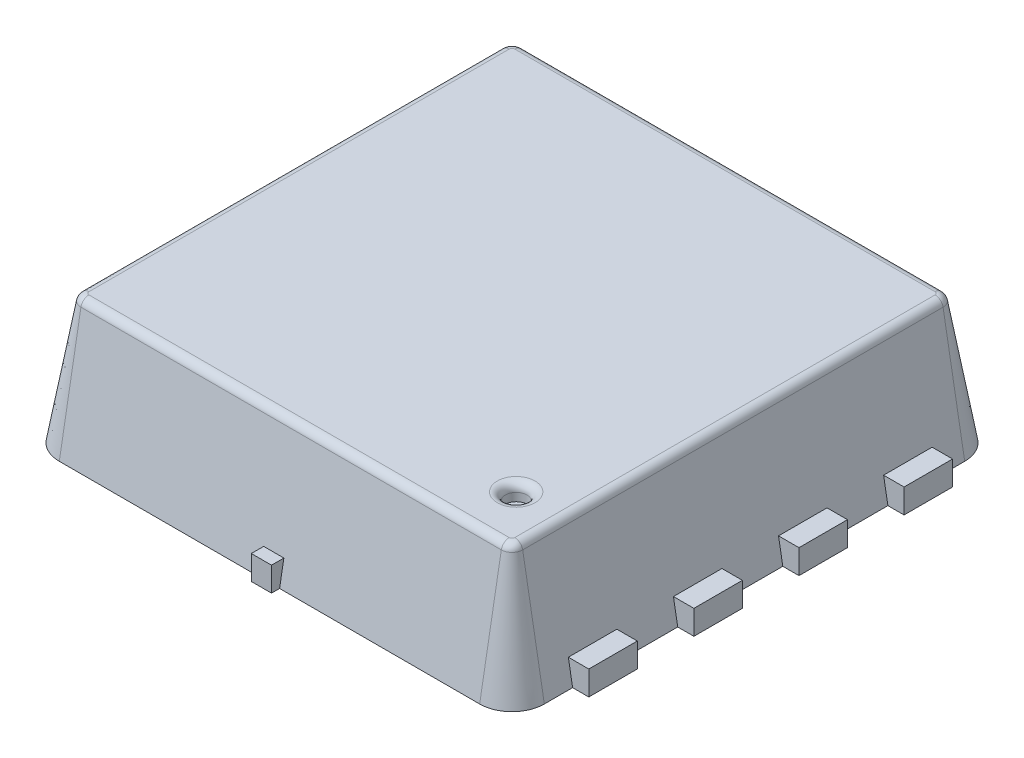
SolidWorks part; units mm, degrees
ref_plane "Front" through (0, 0, 0) normal (0, 0, 1) x (1, 0, 0)
ref_plane "Top" through (0, 0, 0) normal (0, 1, 0) x (1, 0, 0)
ref_plane "Right" through (0, 0, 0) normal (1, 0, 0) x (0, 0, -1)
sketch "Sketch1" plane through (0, 0, 0) normal (0, 1, 0) x (1, 0, 0)
  line L1 (-1.5, -1.5) -> (1.5, -1.5)
  line L2 (-1.5, -1.5) -> (-1.5, 1.5)
  line L3 (-1.5, 1.5) -> (1.5, 1.5)
  line L4 (1.5, -1.5) -> (1.5, 1.5)
  line L5 (-1.5, -1.5) -> (1.5, 1.5) construction
  line L6 (-1.5, 1.5) -> (1.5, -1.5) construction
  point P0 (0, 0)
  point P6 (0, 0)
  dimension "D1" = 3
extrude "Boss-Extrude1" add sketch "Sketch1" along normal blind 0.8
fillet "Fillet1" radius 0.2 4 edges at (-1.5, 0.4, -1.5) (1.5, 0.4, -1.5) (1.5, 0.4, 1.5) (-1.5, 0.4, 1.5)
chamfer "Chamfer1" distance 0.8 angle 10 8 edges at (0, 0.8, 1.5) (-1.5, 0.8, 0) (0, 0.8, -1.5) (1.5, 0.8, 0) (1.4414, 0.8, -1.4414) (1.4414, 0.8, 1.4414) (-1.4414, 0.8, 1.4414) (-1.4414, 0.8, -1.4414) first distance on face at (0, 0.4, 1.5) first distance on face at (-1.5, 0.4, 0) first distance on face at (0, 0.4, -1.5) first distance on face at (1.5, 0.4, 0) first distance on face at (1.4207, 0.4, -1.4207) first distance on face at (1.4207, 0.4, 1.4207) first distance on face at (-1.4207, 0.4, 1.4207) first distance on face at (-1.4207, 0.4, -1.4207)
sketch "Sketch2" plane through (0, 0, 0) normal (0, -1, 0) x (1, 0, 0)
  line L0 (-1.5, -1.3) -> (-1.5, 1.3) construction
  line L1 (-1.6, -1.125) -> (-1.4, -1.125)
  line L2 (-1.6, -1.125) -> (-1.6, -0.825)
  line L3 (-1.6, -0.825) -> (-1.4, -0.825)
  line L4 (-1.4, -1.125) -> (-1.4, -0.825)
  line L5 (-1.6, -1.125) -> (-1.4, -0.825) construction
  line L6 (-1.6, -0.825) -> (-1.4, -1.125) construction
  point P0 (-1.5, -0.975)
  point P7 (-1.5, 0)
  dimension "D1" = 0.3
  dimension "D2" = 0.2
  dimension "D3" = 0.975
extrude "Boss-Extrude2" add sketch "Sketch2" against normal blind 0.15 separate body
pattern_linear "LPattern1" count 4 spacing 0.65 along (0, 0, 1) of "Boss-Extrude2"
ref_plane "Plane1" through (0, 0, 0) normal (-1, 0, 0) x (0, 0, 1)
mirror "Mirror2" about plane through (0, 0, 0) normal (-1, 0, 0) of "LPattern1", "Boss-Extrude2"
sketch "Sketch3" plane through (0, 0.8, 0) normal (0, 1, 0) x (1, 0, 0)
  circle A0 centre (1.0765, -1.0506) radius 0.0667
  point P2 (0, 0)
  point P3 (0, 0)
  point P4 (1.0765, -1.0506)
extrude "Cut-Extrude1" cut sketch "Sketch3" against normal blind 0.1
sketch "Sketch4" plane through (0, 0, 0) normal (0, -1, 0) x (1, 0, 0)
  line L0 (1.3, -1.5) -> (-1.3, -1.5) construction
  line L1 (0.0625, -1.55) -> (-0.0625, -1.55)
  line L2 (0.0625, -1.55) -> (0.0625, -1.45)
  line L3 (0.0625, -1.45) -> (-0.0625, -1.45)
  line L4 (-0.0625, -1.55) -> (-0.0625, -1.45)
  line L5 (0.0625, -1.55) -> (-0.0625, -1.45) construction
  line L6 (0.0625, -1.45) -> (-0.0625, -1.55) construction
  point P0 (0, -1.5)
  dimension "D1" = 0.125
  dimension "D2" = 0.05
extrude "Boss-Extrude3" add sketch "Sketch4" against normal blind 0.15 separate body
ref_plane "Plane2" through (0, 0, 0) normal (0, 0, 1) x (1, 0, 0)
mirror "Mirror7" about plane through (0, 0, 0) normal (0, 0, 1) of bodies 109
fillet "Fillet2" radius 0.05 9 edges at (1.3417, 0.8, 1.3417) (0, 0.8, 1.3589) (-1.3417, 0.8, 1.3417) (-1.3589, 0.8, 0) (-1.3417, 0.8, -1.3417) (0, 0.8, -1.3589) (1.3417, 0.8, -1.3417) (1.3589, 0.8, 0) (1.0765, 0.8, 1.1173)
equation "\"D3@Sketch2\"=1.5*0.65"
